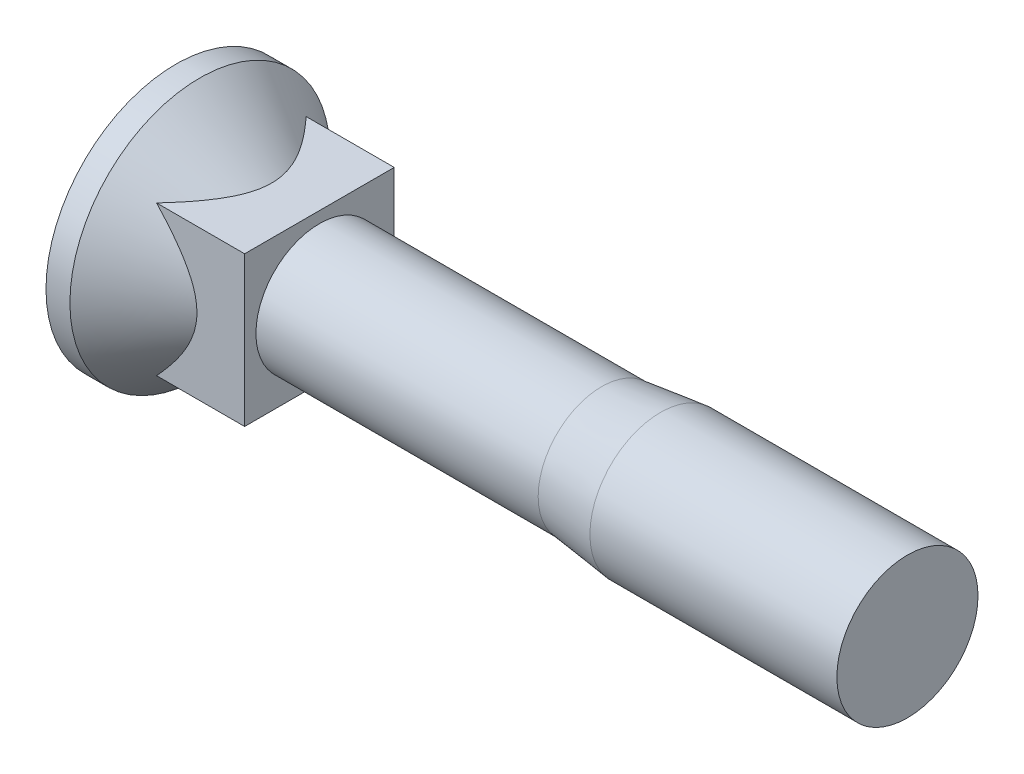
SolidWorks part; units mm, degrees
ref_plane "Front" through (0, 0, 0) normal (0, 0, 1) x (1, 0, 0)
ref_plane "Top" through (0, 0, 0) normal (0, 1, 0) x (1, 0, 0)
ref_plane "Right" through (0, 0, 0) normal (1, 0, 0) x (0, 0, -1)
ref_plane "Plane1" through (6.1, 0, 0) normal (1, 0, 0) x (0, 0, -1)
sketch "Sketch1" plane through (0, 0, 0) normal (0, 0, 1) x (1, 0, 0)
  line L0 (-5.3098, 0) -> (7.9048, 0) construction
  line L1 (0, 5.525) -> (0, 0)
  line L2 (0, 5.525) -> (1.0167, 5.525)
  line L3 (1.0167, 5.525) -> (7.5545, 0.5083)
  line L4 (7.5545, 0.5083) -> (7.5545, 0)
  line L5 (0, 0) -> (7.5545, 0)
  dimension "D1" = 37.5
  dimension "D3" = 0.5083
  dimension "D2" = 1.0167
revolve "BaseHead" add sketch "Sketch1" angle 360 about L0
sketch "Sketch2" plane through (6.1, 0, 0) normal (1, 0, 0) x (0, 0, -1)
  line L1 (3.18, -3.18) -> (3.18, 3.18)
  line L2 (3.18, 3.18) -> (-3.18, 3.18)
  line L3 (-3.18, 3.18) -> (-3.18, -3.18)
  line L4 (-3.18, -3.18) -> (3.18, -3.18)
  circle A0 centre (0, 0) radius 3.18 construction
  dimension "D1" = 6.36
extrude "Neck" add sketch "Sketch2" against normal up to surface (6.1 mm away) up to face at (0, 0, 5.525)
sketch "Sketch3" plane through (6.1, 0, 0) normal (1, 0, 0) x (0, 0, -1)
  circle A0 centre (0, 0) radius 3
extrude "BaseBody" add sketch "Sketch3" along normal blind 25
cosmetic thread "ThreadCosmetic1" [suppressed] parameters "D1"=10.5, "D2"=4.917
sketch "Sketch4" plane through (0, 0, 0) normal (0, 1, 0) x (1, 0, 0)
  line L0 (-1.1729, 0) -> (32.1215, 0) construction
  line L2 (6.1, 2.7) -> (18.1, 2.7)
  line L3 (18.1, 2.7) -> (20.6, 3)
  line L4 (20.6, 3) -> (6.1, 3)
  line L5 (6.1, 3) -> (6.1, 2.7)
  line L6 (31.1, -3) -> (31.1, 3) construction
  line L7 (0, 5.525) -> (0, -5.525) construction
  dimension "D1" = 6
  dimension "D2" = 5.4
  dimension "D4" = 10.5
  dimension "D3" = 6.1
revolve "Cut-Extrude1" cut sketch "Sketch4" angle 360 about L0
sketch "Sketch5" plane through (0, 0, 0) normal (0, 0, 1) x (1, 0, 0)
  line L0 (30.8293, 3) -> (31.1, 2.531)
  line L1 (31.3708, 3.5415) -> (31.3708, 3)
  line L2 (31.1, -3) -> (31.1, 3) construction
  line L3 (31.1, 2.531) -> (31.3708, 3)
  line L4 (30.8293, 3.5415) -> (30.8293, 3)
  line L5 (31.1, 0) -> (0, 0) construction
  line L6 (30.8293, 3.5415) -> (31.3708, 3.5415)
  line L8 (31.1, 3) -> (20.6, 3) construction
revolve "Cut-Revolve10" [suppressed] cut sketch "Sketch5" angle 360 about L5
pattern_linear "LPattern10" [suppressed] count 16 spacing 0.6498 along (-1, 0, 0) of bodies 106
equation "\"D4@Sketch2\" = \"Ss@Sketch2\" / 2"
equation "\"D3@Sketch2\" = \"D4@Sketch2\""
equation "\"D1@Sketch2\" = \"Ss@Sketch2\""
equation "\"D3@Sketch1\" = \"D2@Sketch1\" / 2"
equation "\"D2@Sketch1\" = \"k@Plane1\" / 6"
equation "\"D1@Sketch4\" = \"d@Sketch3\""
equation "\"D2@Sketch4\" =\"d@Sketch3\" * 0.9"
equation "\"D4@Sketch4\" = \"D1@ThreadCosmetic1\""
equation "\"D3@Sketch4\"=\"k@Plane1\""
equation "\"D2@Sketch5\" = (  \"d@Sketch3\" - \"D2@ThreadCosmetic1\" )  / 2"
equation "\"D3@LPattern10\" = \"D2@Sketch5\" * 1.2"
equation "\"D1@LPattern10\" = \"D1@ThreadCosmetic1\" / \"D3@LPattern10\""
